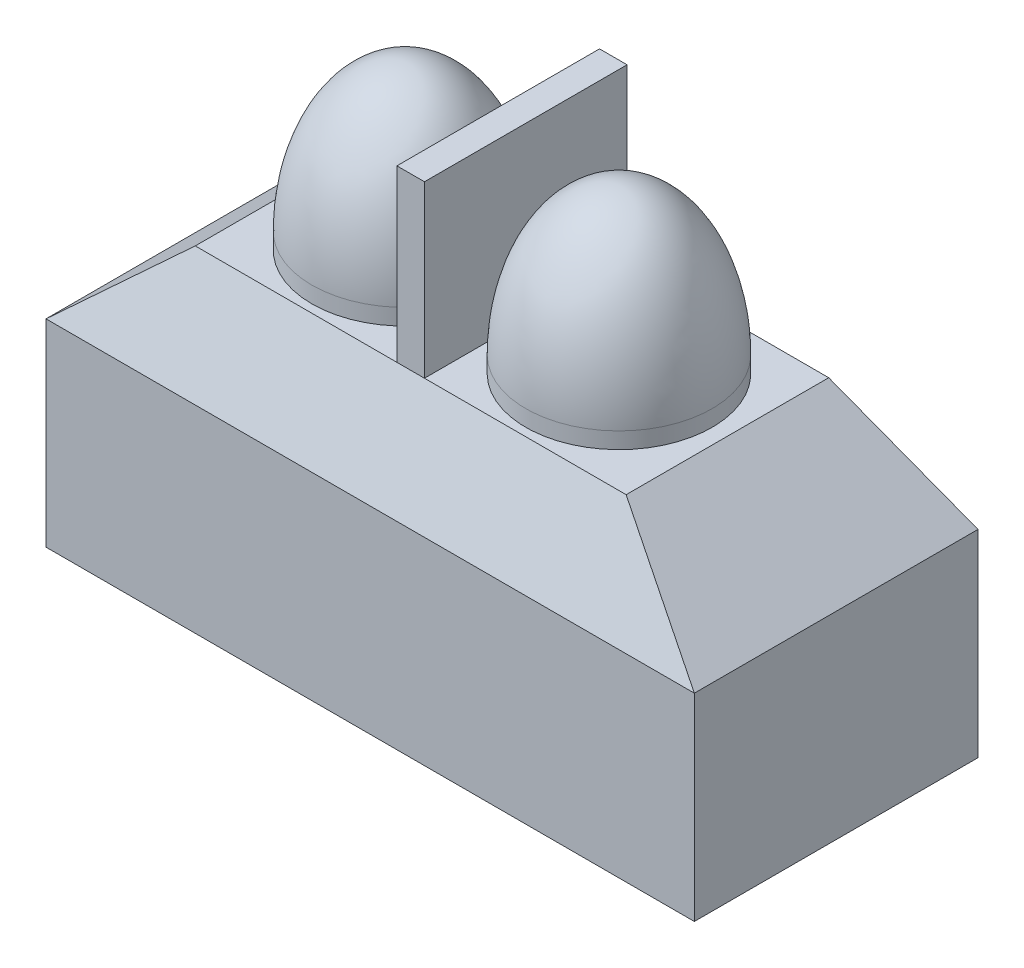
SolidWorks part; units mm, degrees
ref_plane "Front Plane" through (0, 0, 0) normal (0, 0, 1) x (1, 0, 0)
ref_plane "Top Plane" through (0, 0, 0) normal (0, 1, 0) x (1, 0, 0)
ref_plane "Right Plane" through (0, 0, 0) normal (1, 0, 0) x (0, 0, -1)
sketch "Sketch1" plane through (0, 0, 0) normal (0, 1, 0) x (1, 0, 0)
  line L1 (-5.08, -2.2225) -> (5.08, -2.2225)
  line L2 (-5.08, -2.2225) -> (-5.08, 2.2225)
  line L3 (-5.08, 2.2225) -> (5.08, 2.2225)
  line L4 (5.08, -2.2225) -> (5.08, 2.2225)
  line L5 (-5.08, -2.2225) -> (5.08, 2.2225) construction
  line L6 (-5.08, 2.2225) -> (5.08, -2.2225) construction
  point P0 (0, 0)
  dimension "D1" = 10.16
  dimension "D2" = 4.445
extrude "Boss-Extrude1" add sketch "Sketch1" along normal blind 3.0988
sketch "Sketch3" plane through (0, 3.0988, 0) normal (0, 1, 0) x (-1, 0, 0)
  line L0 (-5.08, 2.2225) -> (-5.08, -2.2225) construction
  line L1 (5.08, 2.2225) -> (-5.08, 2.2225)
  line L2 (5.08, 2.2225) -> (5.08, -2.2225)
  line L3 (5.08, -2.2225) -> (-5.08, -2.2225)
  line L4 (-5.08, 2.2225) -> (-5.08, -2.2225)
  line L5 (5.08, 2.2225) -> (-5.08, -2.2225) construction
  line L6 (5.08, -2.2225) -> (-5.08, 2.2225) construction
  line L7 (5.08, 2.2225) -> (-5.08, 2.2225) construction
  point P0 (0, 0)
  point P10 (-2.1167, -2.2225)
  point P11 (1.993, -2.2225)
ref_plane "Plane1" through (0, 3.0988, 0) normal (0, 1, 0) x (-1, 0, 0)
extrude "Boss-Extrude3" add sketch "Sketch3" along normal blind 1.524
sketch "Sketch4" plane through (0, 0, -2.2225) normal (0, 0, -1) x (-1, 0, 0)
  line L0 (-3.3761, 4.6228) -> (-5.08, 3.0988)
  line L1 (-5.08, 4.6228) -> (5.08, 4.6228) construction
  line L2 (-5.08, 4.6228) -> (-5.08, 0) construction
  line L3 (-5.08, 4.6228) -> (-5.08, 3.0988)
  line L4 (-5.08, 4.6228) -> (-3.3761, 4.6228)
  line L5 (2.4447, 3.0988) -> (-2.4447, 3.0988) construction
  line L6 (0, 0) -> (0, 4.6228) construction
  line L7 (5.08, 4.6228) -> (3.3761, 4.6228)
  line L8 (5.08, 4.6228) -> (5.08, 3.0988)
  line L9 (3.3761, 4.6228) -> (5.08, 3.0988)
  dimension "D1" = 2.286
extrude "Cut-Extrude1" cut sketch "Sketch4" against normal through all
sketch "Sketch8" plane through (5.08, 0, 0) normal (1, 0, 0) x (0, 0, -1)
  line L0 (-2.2225, 3.0988) -> (-2.2225, 4.6228)
  line L3 (-2.2225, 4.6228) -> (2.2225, 4.6228) construction
  line L4 (-2.2225, 4.6228) -> (2.2225, 4.6228)
  line L5 (-2.2225, 3.0988) -> (-1.5875, 4.6228)
  line L6 (0, 4.6228) -> (0, 2.9532) construction
  line L7 (2.2225, 3.0988) -> (1.5875, 4.6228)
  line L8 (2.2225, 3.0988) -> (2.2225, 4.6228)
  line L9 (2.4447, 3.0988) -> (-2.4447, 3.0988) construction
  line L10 (-2.2225, 3.0988) -> (-2.2225, 0) construction
  point P7 (-2.2225, 3.0988)
  dimension "D1" = 1.651
extrude "Cut-Extrude3" cut sketch "Sketch8" against normal through all contours L7 L8 L4 | L0 L5 L4 region at (5.08, 4.1148, -2.0108) region at (5.08, 4.1148, 2.0108)
sketch "Sketch9" plane through (0, 4.6228, 0) normal (0, 1, 0) x (-1, 0, 0)
  line L0 (0, 0) -> (0, 1.5875) construction
  line L1 (3.3761, 1.5875) -> (-3.3761, 1.5875) construction
  line L2 (0, 1.5875) -> (0, -1.5875) construction
  line L3 (3.3761, -1.5875) -> (-3.3761, -1.5875) construction
  line L4 (0, 0.6509) -> (-0.2159, 0.6509) construction
  line L5 (-0.2159, -1.5875) -> (0.2159, -1.5875)
  line L6 (-0.2159, -1.5875) -> (-0.2159, 1.5875)
  line L7 (-0.2159, 1.5875) -> (0.2159, 1.5875)
  line L8 (0.2159, -1.5875) -> (0.2159, 1.5875)
  line L9 (0, 0.6509) -> (0.2159, 0.6509) construction
  dimension "D1" = 0.4318
extrude "Boss-Extrude4" add sketch "Sketch9" along normal blind 2.667
sketch "Sketch10" plane through (0, 4.6228, 0) normal (0, 1, 0) x (1, 0, 0)
  line L0 (0, 0) -> (0, -1.5875) construction
  line L1 (-0.2159, -1.5875) -> (0.2159, -1.5875) construction
  line L2 (0, -1.5875) -> (0, 1.5875) construction
  line L3 (0.2159, 1.5875) -> (-0.2159, 1.5875) construction
  line L5 (-0.2159, 1.5875) -> (-0.2159, -1.5875) construction
  circle A0 centre (-1.6764, 0) radius 1.4605
  circle A1 centre (1.6764, 0) radius 1.4605
  dimension "D1" = 2.921
extrude "Boss-Extrude6" add sketch "Sketch10" along normal blind 0.254 separate body
dome "Dome2" faces to dome 1 distance 2.286 reverse direction no elliptical dome yes face at (-1.6764, 4.8768, 1.4605) parameters "D1"=2.286
dome "Dome3" faces to dome 1 distance 2.286 reverse direction no elliptical dome yes face at (1.6764, 4.8768, -1.4605) parameters "D1"=2.286
